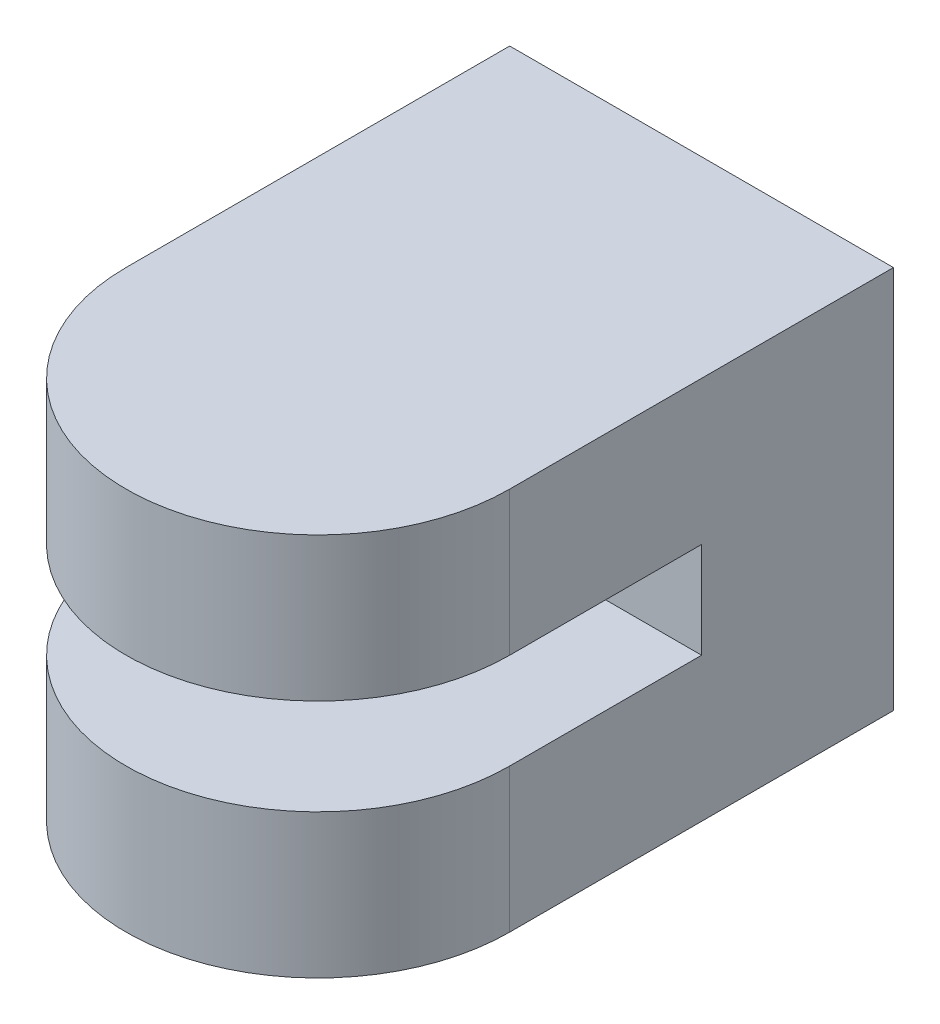
SolidWorks part; units mm, degrees
ref_plane "Ebene vorne" through (0, 0, 0) normal (0, 0, 1) x (1, 0, 0)
ref_plane "Ebene oben" through (0, 0, 0) normal (0, 1, 0) x (1, 0, 0)
ref_plane "Ebene rechts" through (0, 0, 0) normal (1, 0, 0) x (0, 0, -1)
sketch "Skizze1" plane through (0, 0, 0) normal (0, 1, 0) x (1, 0, 0)
  line L2 (-10, 0) -> (-10, 20)
  line L3 (-10, 20) -> (10, 20)
  line L4 (10, 0) -> (10, 20)
  arc A0 (-10, 0) -> (10, 0) centre (0, 0) ccw
  dimension "D1" = 20
  dimension "D2" = 20
extrude "Aufsatz-Linear austragen1" add sketch "Skizze1" along normal mid plane 20
sketch "Skizze2" plane through (0, 0, 0) normal (0, 0, 1) x (1, 0, 0)
  line L0 (10, 10) -> (10, -10) construction
  line L1 (-10, -2.5) -> (10, -2.5)
  line L2 (-10, -2.5) -> (-10, 2.5)
  line L3 (-10, 2.5) -> (10, 2.5)
  line L4 (10, -2.5) -> (10, 2.5)
  line L5 (-10, -2.5) -> (10, 2.5) construction
  line L6 (-10, 2.5) -> (10, -2.5) construction
  point P0 (0, 0)
  dimension "D1" = 5
extrude "Schnitt-Linear austragen1" cut sketch "Skizze2" along normal through all and the other way blind 10
ref_axis "Achse1" through (0, 11, 0) along (0, -1, 0)
